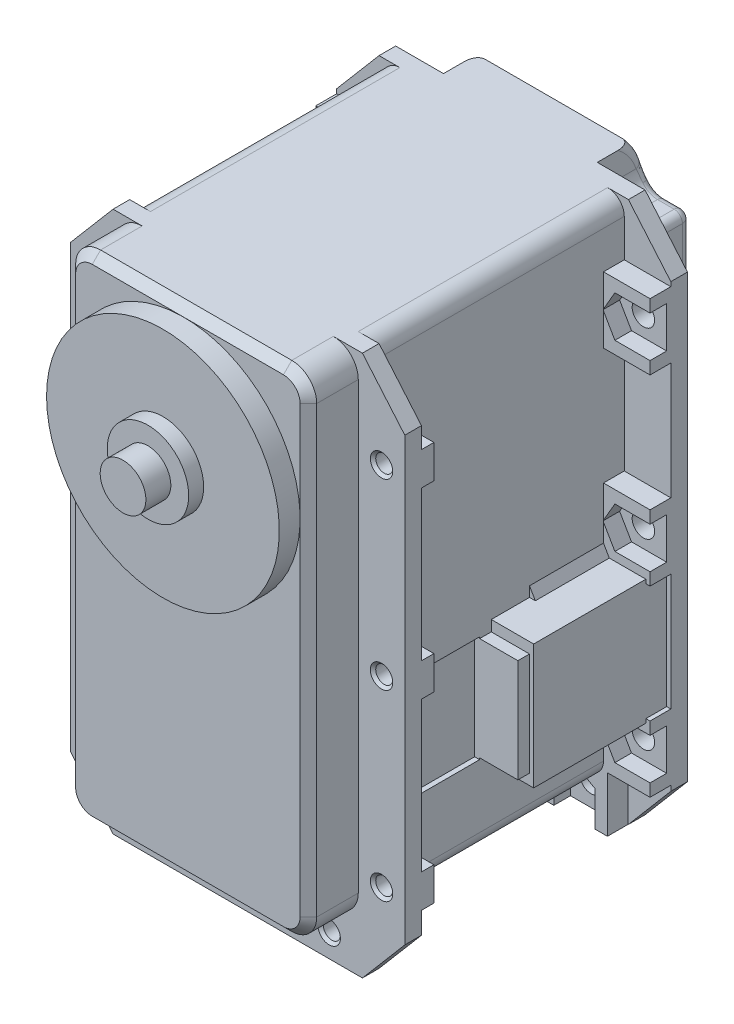
SolidWorks part; units mm, degrees
note: '?' marks a value the reader was unsure of.
material "Custom Plastic"
ref_plane "Front Plane" through (0, 0, 0) normal (0, 0, 1) x (1, 0, 0)
ref_plane "Top Plane" through (0, 0, 0) normal (0, 1, 0) x (1, 0, 0)
ref_plane "Right Plane" through (0, 0, 0) normal (1, 0, 0) x (0, 0, -1)
ref_plane "Plane1" through (9.25, 0, 0) normal (1, 0, 0) x (0, 0, -1)
sketch "Sketch1" plane through (9.25, 0, 0) normal (1, 0, 0) x (0, 0, -1)
  line L0 (21, 14.5) -> (21, 9.5)
  line L1 (21, 9.5) -> (23, 9.5)
  arc A0 (23, 9.5) -> (21, 14.5) centre (15.75, 9.5) ccw
extrude "Boss-Extrude1" add sketch "Sketch1" against normal blind 18.5
ref_plane "Plane2" through (0, 9.5, 0) normal (0, -1, 0) x (1, 0, 0)
sketch "Sketch2" plane through (0, 9.5, 0) normal (0, -1, 0) x (1, 0, 0)
  line L0 (-15.8711, -21) -> (-15.8711, -23)
  line L1 (-15.8711, -23) -> (-9.25, -23)
  line L2 (-9.25, -23) -> (-9.25, -21)
  line L3 (-9.25, -21) -> (-15.8711, -21)
extrude "Boss-Extrude2" add sketch "Sketch2" against normal blind 5
sketch "Sketch3" plane through (0, 9.5, 0) normal (0, -1, 0) x (1, 0, 0)
  line L0 (9.25, -21) -> (9.25, -23)
  line L1 (9.25, -23) -> (20.1, -23)
  line L2 (20.1, -23) -> (20.1, -21)
  line L3 (20.1, -21) -> (9.25, -21)
extrude "Boss-Extrude3" add sketch "Sketch3" against normal blind 5
sketch "Sketch4" plane through (0, 9.5, 0) normal (0, -1, 0) x (1, 0, 0)
  line L0 (20.1, -21) -> (20.1, -23)
  line L1 (20.1, -23) -> (-15.8711, -23)
  line L2 (-15.8711, -23) -> (-15.8711, -21)
  line L3 (-15.8711, -21) -> (20.1, -21)
extrude "Boss-Extrude4" add sketch "Sketch4" along normal blind 60.1
sketch "Sketch5" plane through (0, 0, -21) normal (0, 0, 1) x (1, 0, 0)
  line L0 (-15.8711, -50.6) -> (-15.8711, 14.5)
  line L1 (-15.8711, 14.5) -> (20.1, 14.5)
  line L2 (20.1, 14.5) -> (20.1, -50.6)
  line L3 (20.1, -50.6) -> (-15.8711, -50.6)
extrude "Boss-Extrude5" add sketch "Sketch5" along normal blind 6.5
sketch "Sketch6" plane through (0, 0, -23) normal (0, 0, -1) x (-1, 0, 0)
  line L0 (15.8711, -50.6) -> (15.8711, 14.5)
  line L1 (15.8711, 14.5) -> (9.25, 14.5)
  line L2 (9.25, 14.5) -> (9.25, -45)
  line L3 (9.25, -45) -> (-9.25, -45)
  line L4 (-9.25, -45) -> (-9.25, 14.5)
  line L5 (-9.25, 14.5) -> (-20.1, 14.5)
  line L6 (-20.1, 14.5) -> (-20.1, -50.6)
  line L7 (-20.1, -50.6) -> (15.8711, -50.6)
extrude "Cut-Extrude1" cut sketch "Sketch6" against normal blind 2
sketch "Sketch7" plane through (0, 0, -14.5) normal (0, 0, 1) x (1, 0, 0)
  line L0 (-15.8711, -20.475) -> (-14.5, -18.1003)
  line L1 (-14.5, -18.1003) -> (-14.5, -17.8997)
  line L2 (-14.5, -17.8997) -> (-15.8711, -15.525)
  line L3 (-15.8711, -15.525) -> (-15.8711, 1.525)
  line L4 (-15.8711, 1.525) -> (-14.5, 3.8997)
  line L5 (-14.5, 3.8997) -> (-14.5, 4.1003)
  line L6 (-14.5, 4.1003) -> (-15.8711, 6.475)
  line L7 (-15.8711, 6.475) -> (-15.8711, 14.5)
  line L8 (-15.8711, 14.5) -> (20.1, 14.5)
  line L9 (20.1, 14.5) -> (20.1, -50.6)
  line L10 (20.1, -50.6) -> (-15.8711, -50.6)
  line L11 (-15.8711, -50.6) -> (-15.8711, -42.475)
  line L12 (-15.8711, -42.475) -> (-14.5, -40.1003)
  line L13 (-14.5, -40.1003) -> (-14.5, -39.8997)
  line L14 (-14.5, -39.8997) -> (-15.8711, -37.525)
  line L15 (-15.8711, -37.525) -> (-15.8711, -20.475)
extrude "Boss-Extrude6" add sketch "Sketch7" along normal blind 2
sketch "Sketch8" plane through (0, 0, -21) normal (0, 0, -1) x (-1, 0, 0)
  line L0 (15.8711, -50.6) -> (15.8711, 14.5)
  line L1 (15.8711, 14.5) -> (9.25, 14.5)
  line L2 (9.25, 14.5) -> (9.25, -45)
  line L3 (9.25, -45) -> (-9.25, -45)
  line L4 (-9.25, -45) -> (-9.25, 14.5)
  line L5 (-9.25, 14.5) -> (-20.1, 14.5)
  line L6 (-20.1, 14.5) -> (-20.1, -50.6)
  line L7 (-20.1, -50.6) -> (15.8711, -50.6)
extrude "Cut-Extrude2" cut sketch "Sketch8" against normal blind 4
sketch "Sketch9" plane through (0, 0, -12.5) normal (0, 0, 1) x (1, 0, 0)
  line L0 (20.1, 14.5) -> (20.1, -50.6)
  line L1 (20.1, -50.6) -> (-15.8711, -50.6)
  line L2 (-15.8711, -50.6) -> (-15.8711, -42.475)
  line L3 (-15.8711, -42.475) -> (-14.5, -40.1003)
  line L4 (-14.5, -40.1003) -> (-14.5, 14.5)
  line L5 (-14.5, 14.5) -> (20.1, 14.5)
extrude "Boss-Extrude7" add sketch "Sketch9" along normal blind 29.5
sketch "Sketch10" plane through (0, 0, 17) normal (0, 0, 1) x (1, 0, 0)
  line L0 (14.5, 14.5) -> (14.5, -45)
  line L1 (14.5, -45) -> (-14.5, -45)
  line L2 (-14.5, -45) -> (-14.5, -40.1003)
  line L3 (-14.5, -40.1003) -> (-15.8711, -42.475)
  line L4 (-15.8711, -42.475) -> (-15.8711, -50.6)
  line L5 (-15.8711, -50.6) -> (20.1, -50.6)
  line L6 (20.1, -50.6) -> (20.1, 14.5)
  line L7 (20.1, 14.5) -> (14.5, 14.5)
extrude "Cut-Extrude3" cut sketch "Sketch10" against normal blind 29.5
sketch "Sketch11" plane through (0, 0, -12.5) normal (0, 0, 1) x (1, 0, 0)
  line L0 (-13.475, -46.3711) -> (-13.475, -50.6)
  line L1 (-13.475, -50.6) -> (-8.525, -50.6)
  line L2 (-8.525, -50.6) -> (-8.525, -46.3711)
  line L3 (-8.525, -46.3711) -> (-11, -44.9421)
  line L4 (-11, -44.9421) -> (-13.475, -46.3711)
extrude "Cut-Extrude4" cut sketch "Sketch11" against normal blind 2
sketch "Sketch12" plane through (0, 0, -12.5) normal (0, 0, 1) x (1, 0, 0)
  line L0 (8.525, -46.3711) -> (8.525, -50.6)
  line L1 (8.525, -50.6) -> (13.475, -50.6)
  line L2 (13.475, -50.6) -> (13.475, -46.3711)
  line L3 (13.475, -46.3711) -> (11, -44.9421)
  line L4 (11, -44.9421) -> (8.525, -46.3711)
extrude "Cut-Extrude5" cut sketch "Sketch12" against normal blind 2
sketch "Sketch13" plane through (0, 0, -12.5) normal (0, 0, 1) x (1, 0, 0)
  line L0 (15.8711, -42.475) -> (20.1, -42.475)
  line L1 (20.1, -42.475) -> (20.1, -37.525)
  line L2 (20.1, -37.525) -> (15.8711, -37.525)
  line L3 (15.8711, -37.525) -> (14.4421, -40)
  line L4 (14.4421, -40) -> (15.8711, -42.475)
extrude "Cut-Extrude6" cut sketch "Sketch13" against normal blind 2
sketch3d "3DSketch1"
  point P0 (0.3206, -15.6432, -2.4982)
  point P1 (0.3206, 84.3568, -2.4982)
ref_axis "Axis1" through (0.3206, -15.6432, -2.4982) along (0, 1, 0)?
pattern_linear "LPattern1" count 3 spacing 22 along (0, 1, 0) of "Cut-Extrude6"
ref_plane "Plane3" through (0, 0, -14.5) normal (0, 0, -1) x (-1, 0, 0)
sketch "Sketch14" plane through (0, 0, -14.5) normal (0, 0, -1) x (-1, 0, 0)
  line L0 (14.4421, -40) -> (14.5, -40.1003)
  line L1 (14.5, -40.1003) -> (14.5, -39.8997)
  line L2 (14.5, -39.8997) -> (14.4421, -40)
extrude "Cut-Extrude7" cut sketch "Sketch14" against normal blind 2
sketch3d "3DSketch2"
  point P0 (0.2957, -15.6557, -2.4823)
  point P1 (0.2957, 84.3443, -2.4823)
ref_axis "Axis2" through (0.2957, -15.6557, -2.4823) along (0, 1, 0)?
pattern_linear "LPattern2" count 3 spacing 22 along (0, 1, 0) of "Cut-Extrude7"
sketch "Sketch15" plane through (-15.8711, 0, 0) normal (-1, 0, 0) x (0, 0, 1)
  line L0 (-12.5, 14.5) -> (-12.5, 6.475)
  line L1 (-12.5, 6.475) -> (-14.5, 6.475)
  line L2 (-14.5, 6.475) -> (-14.5, 1.525)
  line L3 (-14.5, 1.525) -> (-12.5, 1.525)
  line L4 (-12.5, 1.525) -> (-12.5, -15.525)
  line L5 (-12.5, -15.525) -> (-14.5, -15.525)
  line L6 (-14.5, -15.525) -> (-14.5, -20.475)
  line L7 (-14.5, -20.475) -> (-12.5, -20.475)
  line L8 (-12.5, -20.475) -> (-12.5, -37.525)
  line L9 (-12.5, -37.525) -> (-14.5, -37.525)
  line L10 (-14.5, -37.525) -> (-14.5, -42.475)
  line L11 (-14.5, -42.475) -> (-12.5, -42.475)
  line L12 (-12.5, -42.475) -> (-12.5, -50.6)
  line L13 (-12.5, -50.6) -> (-17, -50.6)
  line L14 (-17, -50.6) -> (-17, 14.5)
  line L15 (-17, 14.5) -> (-12.5, 14.5)
extrude "Boss-Extrude8" add sketch "Sketch15" along normal blind 4.2289
sketch "Sketch16" plane through (-14.5, 0, 0) normal (-1, 0, 0) x (0, 0, 1)
  line L0 (15, -45) -> (15, 14.5)
  line L1 (15, 14.5) -> (17, 14.5)
  line L2 (17, 14.5) -> (17, -45)
  line L3 (17, -45) -> (15, -45)
extrude "Boss-Extrude9" add sketch "Sketch16" along normal blind 5.6
sketch "Sketch17" plane through (0, -45, 0) normal (0, -1, 0) x (1, 0, 0)
  line L0 (14.5, 15) -> (-20.1, 15)
  line L1 (-20.1, 15) -> (-20.1, 17)
  line L2 (-20.1, 17) -> (14.5, 17)
  line L3 (14.5, 17) -> (14.5, 15)
extrude "Boss-Extrude10" add sketch "Sketch17" along normal blind 5.6
sketch "Sketch18" plane through (14.5, 0, 0) normal (1, 0, 0) x (0, 0, -1)
  line L0 (-15, -50.6) -> (-17, -50.6)
  line L1 (-17, -50.6) -> (-17, 14.5)
  line L2 (-17, 14.5) -> (-15, 14.5)
  line L3 (-15, 14.5) -> (-15, -50.6)
extrude "Boss-Extrude11" add sketch "Sketch18" along normal blind 5.6
sketch "Sketch19" plane through (14.5, 0, 0) normal (1, 0, 0) x (0, 0, -1)
  line L0 (-1, -21.5) -> (12.5, -21.5)
  line L1 (12.5, -21.5) -> (12.5, -36.5)
  line L2 (12.5, -36.5) -> (-1, -36.5)
  line L3 (-1, -36.5) -> (-1, -21.5)
extrude "Boss-Extrude12" add sketch "Sketch19" along normal blind 5.1
sketch "Sketch20" plane through (0, 0, 1) normal (0, 0, 1) x (1, 0, 0)
  line L0 (19.1, -35.21) -> (14.5, -35.21)
  line L1 (14.5, -35.21) -> (14.5, -22.79)
  line L2 (14.5, -22.79) -> (19.1, -22.79)
  line L3 (19.1, -22.79) -> (19.1, -35.21)
extrude "Boss-Extrude13" add sketch "Sketch20" along normal blind 1.4
sketch "Sketch21" plane through (14.5, 0, 0) normal (1, 0, 0) x (0, 0, -1)
  line L0 (-2.4, -35.4) -> (-2.4, -22.6)
  line L1 (-2.4, -22.6) -> (-12.5, -22.6)
  line L2 (-12.5, -22.6) -> (-12.5, -35.4)
  line L3 (-12.5, -35.4) -> (-2.4, -35.4)
extrude "Cut-Extrude8" cut sketch "Sketch21" against normal blind 0.6
sketch "Sketch22" plane through (-14.5, 0, 0) normal (-1, 0, 0) x (0, 0, 1)
  line L0 (1, -36.5) -> (-12.5, -36.5)
  line L1 (-12.5, -36.5) -> (-12.5, -21.5)
  line L2 (-12.5, -21.5) -> (1, -21.5)
  line L3 (1, -21.5) -> (1, -36.5)
extrude "Boss-Extrude14" add sketch "Sketch22" along normal blind 5.1
sketch "Sketch23" plane through (0, 0, 1) normal (0, 0, 1) x (1, 0, 0)
  line L0 (-19.1, -22.79) -> (-14.5, -22.79)
  line L1 (-14.5, -22.79) -> (-14.5, -35.21)
  line L2 (-14.5, -35.21) -> (-19.1, -35.21)
  line L3 (-19.1, -35.21) -> (-19.1, -22.79)
extrude "Boss-Extrude15" add sketch "Sketch23" along normal blind 1.4
sketch "Sketch24" plane through (-14.5, 0, 0) normal (-1, 0, 0) x (0, 0, 1)
  line L0 (2.4, -22.6) -> (2.4, -35.4)
  line L1 (2.4, -35.4) -> (12.5, -35.4)
  line L2 (12.5, -35.4) -> (12.5, -22.6)
  line L3 (12.5, -22.6) -> (2.4, -22.6)
extrude "Cut-Extrude9" cut sketch "Sketch24" against normal blind 0.6
sketch "Sketch25" plane through (0, -50.6, 0) normal (0, -1, 0) x (1, 0, 0)
  line L0 (7.025, -15) -> (7.025, -12.5)
  line L1 (7.025, -12.5) -> (-7.025, -12.5)
  line L2 (-7.025, -12.5) -> (-7.025, -15)
  line L3 (-7.025, -15) -> (7.025, -15)
extrude "Cut-Extrude10" cut sketch "Sketch25" against normal blind 5.6
sketch "Sketch26" plane through (20.1, 0, 0) normal (1, 0, 0) x (0, 0, -1)
  line L0 (15, -21.975) -> (12.5, -21.975)
  line L1 (12.5, -21.975) -> (12.5, -36.025)
  line L2 (12.5, -36.025) -> (15, -36.025)
  line L3 (15, -36.025) -> (15, -21.975)
extrude "Cut-Extrude11" cut sketch "Sketch26" against normal blind 0.5
sketch "Sketch27" plane through (20.1, 0, 0) normal (1, 0, 0) x (0, 0, -1)
  line L0 (15, 0.025) -> (12.5, 0.025)
  line L1 (12.5, 0.025) -> (12.5, -14.025)
  line L2 (12.5, -14.025) -> (15, -14.025)
  line L3 (15, -14.025) -> (15, 0.025)
extrude "Cut-Extrude12" cut sketch "Sketch27" against normal blind 5.6
sketch "Sketch28" plane through (20.1, 0, 0) normal (1, 0, 0) x (0, 0, -1)
  line L0 (12.5, 7.975) -> (15, 7.975)
  line L1 (15, 7.975) -> (15, 14.5)
  line L2 (15, 14.5) -> (12.5, 14.5)
  line L3 (12.5, 14.5) -> (12.5, 7.975)
extrude "Cut-Extrude13" cut sketch "Sketch28" against normal blind 5.6
sketch "Sketch29" plane through (-20.1, 0, 0) normal (-1, 0, 0) x (0, 0, 1)
  line L0 (-15, 7.975) -> (-12.5, 7.975)
  line L1 (-12.5, 7.975) -> (-12.5, 14.5)
  line L2 (-12.5, 14.5) -> (-15, 14.5)
  line L3 (-15, 14.5) -> (-15, 7.975)
extrude "Cut-Extrude14" cut sketch "Sketch29" against normal blind 5.6
sketch "Sketch30" plane through (-20.1, 0, 0) normal (-1, 0, 0) x (0, 0, 1)
  line L0 (-12.5, 0.025) -> (-15, 0.025)
  line L1 (-15, 0.025) -> (-15, -14.025)
  line L2 (-15, -14.025) -> (-12.5, -14.025)
  line L3 (-12.5, -14.025) -> (-12.5, 0.025)
extrude "Cut-Extrude15" cut sketch "Sketch30" against normal blind 5.6
sketch "Sketch31" plane through (-20.1, 0, 0) normal (-1, 0, 0) x (0, 0, 1)
  line L0 (-15, -36.025) -> (-12.5, -36.025)
  line L1 (-12.5, -36.025) -> (-12.5, -21.975)
  line L2 (-12.5, -21.975) -> (-15, -21.975)
  line L3 (-15, -21.975) -> (-15, -36.025)
extrude "Cut-Extrude16" cut sketch "Sketch31" against normal blind 0.5
sketch "Sketch32" plane through (0, -45, 0) normal (0, -1, 0) x (1, 0, 0)
  line L0 (-13, 13.5) -> (-13, 15)
  line L1 (-13, 15) -> (-9, 15)
  line L2 (-9, 15) -> (-9, 13.5)
  line L3 (-9, 13.5) -> (-13, 13.5)
extrude "Boss-Extrude16" add sketch "Sketch32" along normal blind 5.6
sketch "Sketch33" plane through (0, -45, 0) normal (0, -1, 0) x (1, 0, 0)
  line L0 (9, 13.5) -> (9, 15)
  line L1 (9, 15) -> (13, 15)
  line L2 (13, 15) -> (13, 13.5)
  line L3 (13, 13.5) -> (9, 13.5)
extrude "Boss-Extrude17" add sketch "Sketch33" along normal blind 5.6
sketch "Sketch34" plane through (14.5, 0, 0) normal (1, 0, 0) x (0, 0, -1)
  line L0 (-13.5, 2) -> (-15, 2)
  line L1 (-15, 2) -> (-15, 6)
  line L2 (-15, 6) -> (-13.5, 6)
  line L3 (-13.5, 6) -> (-13.5, 2)
extrude "Boss-Extrude18" add sketch "Sketch34" along normal blind 5.6
sketch3d "3DSketch3"
  point P0 (0.0081, -16.3123, -2.1724)
  point P1 (0.0081, -116.3123, -2.1724)
ref_axis "Axis3" through (0.0081, -16.3123, -2.1724) along (0, -1, 0)?
pattern_linear "LPattern3" count 3 spacing 22 along (0, -1, 0) of "Boss-Extrude18"
sketch "Sketch35" plane through (-14.5, 0, 0) normal (-1, 0, 0) x (0, 0, 1)
  line L0 (15, 2) -> (13.5, 2)
  line L1 (13.5, 2) -> (13.5, 6)
  line L2 (13.5, 6) -> (15, 6)
  line L3 (15, 6) -> (15, 2)
extrude "Boss-Extrude19" add sketch "Sketch35" along normal blind 5.6
pattern_linear "LPattern4" count 3 spacing 22 along (0, -1, 0) of "Boss-Extrude19"
sketch "Sketch36" plane through (0, 0, -17) normal (0, 0, -1) x (-1, 0, 0)
  line L0 (-14.5, 9.25) -> (-9.25, 9.25)
  line L1 (-9.25, 9.25) -> (-9.25, -39.75)
  line L2 (-9.25, -39.75) -> (-14.5, -39.75)
  line L3 (-14.5, -39.75) -> (-14.5, 9.25)
extrude "Boss-Extrude20" add sketch "Sketch36" along normal blind 6
sketch "Sketch37" plane through (0, 0, -17) normal (0, 0, -1) x (-1, 0, 0)
  line L0 (14.5, -39.75) -> (9.25, -39.75)
  line L1 (9.25, -39.75) -> (9.25, 9.25)
  line L2 (9.25, 9.25) -> (14.5, 9.25)
  line L3 (14.5, 9.25) -> (14.5, -39.75)
extrude "Boss-Extrude21" add sketch "Sketch37" along normal blind 6
sketch "Sketch38" plane through (0, 0, -12.5) normal (0, 0, 1) x (1, 0, 0)
  line L0 (15.2, -21.5) -> (14.5, -21.5)
  line L1 (14.5, -21.5) -> (14.5, -20.2876)
  line L2 (14.5, -20.2876) -> (15.2, -21.5)
extrude "Boss-Extrude22" add sketch "Sketch38" along normal blind 8.9
sketch "Sketch39" plane through (0, 0, -12.5) normal (0, 0, 1) x (1, 0, 0)
  line L0 (14.975, -43.975) -> (14.975, -50.6)
  line L1 (14.975, -50.6) -> (20.1, -50.6)
  line L2 (20.1, -50.6) -> (20.1, -43.975)
  line L3 (20.1, -43.975) -> (14.975, -43.975)
extrude "Cut-Extrude17" cut sketch "Sketch39" against normal blind 2.5
sketch "Sketch40" plane through (0, -50.6, 0) normal (0, -1, 0) x (1, 0, 0)
  line L0 (-20.1, -15) -> (-14.975, -15)
  line L1 (-14.975, -15) -> (-14.975, -12.5)
  line L2 (-14.975, -12.5) -> (-20.1, -12.5)
  line L3 (-20.1, -12.5) -> (-20.1, -15)
extrude "Cut-Extrude18" cut sketch "Sketch40" against normal blind 6.625
sketch "Sketch41" plane through (0, 0, 17) normal (0, 0, 1) x (1, 0, 0)
  line L0 (-14.5, -45) -> (-14.5, 14.5)
  line L1 (-14.5, 14.5) -> (14.5, 14.5)
  line L2 (14.5, 14.5) -> (14.5, -45)
  line L3 (14.5, -45) -> (-14.5, -45)
extrude "Boss-Extrude23" add sketch "Sketch41" along normal blind 6
sketch "Sketch42" plane through (0, 0, -12.5) normal (0, 0, 1) x (1, 0, 0)
  line L0 (-15.2, -21.5) -> (-14.5, -20.2876)
  line L1 (-14.5, -20.2876) -> (-14.5, -21.5)
  line L2 (-14.5, -21.5) -> (-15.2, -21.5)
extrude "Boss-Extrude24" add sketch "Sketch42" along normal blind 8.9
sketch "Sketch43" plane through (-14.5, 0, 0) normal (-1, 0, 0) x (0, 0, 1)
  line L0 (-8.8, -13.45) -> (-5, -13.45)
  line L1 (-5, -13.45) -> (-5, -7.55)
  line L2 (-5, -7.55) -> (-8.8, -7.55)
  line L3 (-8.8, -7.55) -> (-8.8, -13.45)
extrude "Cut-Extrude19" cut sketch "Sketch43" against normal blind 1
hole_wizard "Hole1" positions "Sketch45" profile "Sketch44" legacy
sketch "Sketch45" plane through (0, 0, -23) normal (0, 0, -1) x (-1, 0, 0)
  point P0 (0, 0)
sketch "Sketch44" plane through (0, 0, -23) normal (1, 0, 0) x (0, 1, 0)
  line L0 (0, 0) -> (0, 1)
  line L1 (0, 1) -> (7.5, 1)
  line L2 (7.5, 1) -> (7.5, 0)
  line L3 (7.5, 0) -> (0, 0)
  line L4 (0, 110) -> (0, -10) construction
  dimension "Diameter" = 15
  dimension "Depth" = 1
ref_plane "Plane4" through (0, 0, 0) normal (0, -1, 0) x (1, 0, 0)
sketch "Sketch46" plane through (0, 0, 0) normal (0, -1, 0) x (1, 0, 0)
  line L0 (2.75, 30.8) -> (0, 30.8)
  line L1 (0, 30.8) -> (0, 23)
  line L2 (0, 23) -> (5, 23)
  line L3 (5, 23) -> (5, 23.5)
  line L4 (5, 23.5) -> (14, 23.5)
  line L5 (14, 23.5) -> (14, 26)
  line L6 (14, 26) -> (5, 26)
  line L7 (5, 26) -> (5, 27.8)
  line L8 (5, 27.8) -> (2.75, 27.8)
  line L9 (2.75, 27.8) -> (2.75, 30.8)
  line L10 (0, 30.8) -> (0, 23) construction
revolve "Revolve1" add sketch "Sketch46" angle 360 about L10 reverse direction yes
sketch "Sketch47" plane through (0, 0, 0) normal (0, -1, 0) x (1, 0, 0)
  line L0 (5, -22) -> (0, -22)
  line L1 (0, -22) -> (0, -24.5)
  line L2 (0, -24.5) -> (4, -24.5)
  line L3 (4, -24.5) -> (4, -22.3)
  line L4 (4, -22.3) -> (5, -22.3)
  line L5 (5, -22.3) -> (5, -22)
  line L6 (0, -22) -> (0, -24.5) construction
revolve "Revolve2" add sketch "Sketch47" angle 360 about L6 reverse direction yes
hole_wizard "Hole2" positions "Sketch49" profile "Sketch48" legacy
sketch "Sketch49" plane through (0, 0, -14.5) normal (0, 0, 1) x (1, 0, 0)
  point P0 (17.3, -40)
sketch "Sketch48" plane through (17.3, -40, -14.5) normal (1, 0, 0) x (0, -1, 0)
  line L0 (0, 0) -> (0, 10)
  line L1 (0, 10) -> (1.35, 10)
  line L2 (1.35, 10) -> (1.35, 0)
  line L3 (1.35, 0) -> (0, 0)
  line L4 (0, 110) -> (0, -10) construction
  dimension "Diameter" = 2.7
  dimension "Depth" = 10
sketch3d "3DSketch4"
  point P0 (0.0008, -15.7705, 0.4564)
  point P1 (0.0008, 84.2295, 0.4564)
ref_axis "Axis4" through (0.0008, -15.7705, 0.4564) along (0, 1, 0)?
pattern_linear "LPattern5" count 3 spacing 22 along (0, 1, 0) of "Hole2"
hole_wizard "Hole3" positions "Sketch51" profile "Sketch50" legacy
sketch "Sketch51" plane through (0, 0, -14.5) normal (0, 0, 1) x (1, 0, 0)
  point P0 (-17.3, -40)
sketch "Sketch50" plane through (-17.3, -40, -14.5) normal (1, 0, 0) x (0, -1, 0)
  line L0 (0, 0) -> (0, 10)
  line L1 (0, 10) -> (1.35, 10)
  line L2 (1.35, 10) -> (1.35, 0)
  line L3 (1.35, 0) -> (0, 0)
  line L4 (0, 110) -> (0, -10) construction
  dimension "Diameter" = 2.7
  dimension "Depth" = 10
sketch3d "3DSketch5"
  point P0 (-0.0021, -15.7694, 0.4644)
  point P1 (-0.0021, 84.2306, 0.4644)
ref_axis "Axis5" through (-0.0021, -15.7694, 0.4644) along (0, 1, 0)?
pattern_linear "LPattern6" count 3 spacing 22 along (0, 1, 0) of "Hole3"
hole_wizard "Hole4" positions "Sketch53" profile "Sketch52" legacy
sketch "Sketch53" plane through (0, 0, -14.5) normal (0, 0, 1) x (1, 0, 0)
  point P0 (11, -47.8)
sketch "Sketch52" plane through (11, -47.8, -14.5) normal (1, 0, 0) x (0, -1, 0)
  line L0 (0, 0) -> (0, 10)
  line L1 (0, 10) -> (1.35, 10)
  line L2 (1.35, 10) -> (1.35, 0)
  line L3 (1.35, 0) -> (0, 0)
  line L4 (0, 110) -> (0, -10) construction
  dimension "Diameter" = 2.7
  dimension "Depth" = 10
hole_wizard "Hole5" positions "Sketch55" profile "Sketch54" legacy
sketch "Sketch55" plane through (0, 0, -14.5) normal (0, 0, 1) x (1, 0, 0)
  point P0 (-11, -47.8)
sketch "Sketch54" plane through (-11, -47.8, -14.5) normal (1, 0, 0) x (0, -1, 0)
  line L0 (0, 0) -> (0, 10)
  line L1 (0, 10) -> (1.35, 10)
  line L2 (1.35, 10) -> (1.35, 0)
  line L3 (1.35, 0) -> (0, 0)
  line L4 (0, 110) -> (0, -10) construction
  dimension "Diameter" = 2.7
  dimension "Depth" = 10
hole_wizard "Hole6" positions "Sketch57" profile "Sketch56" legacy
sketch "Sketch57" plane through (0, 0, 17) normal (0, 0, 1) x (1, 0, 0)
  point P0 (-11, -47.8)
sketch "Sketch56" plane through (-11, -47.8, 17) normal (1, 0, 0) x (0, -1, 0)
  line L0 (0, 0) -> (0, 41.5)
  line L1 (0, 41.5) -> (1.025, 41.5)
  line L2 (1.025, 41.5) -> (1.025, 0)
  line L3 (1.025, 0) -> (0, 0)
  line L4 (0, 110) -> (0, -10) construction
  dimension "Diameter" = 2.05
  dimension "Depth" = 41.5
hole_wizard "Hole7" positions "Sketch59" profile "Sketch58" legacy
sketch "Sketch59" plane through (0, 0, 17) normal (0, 0, 1) x (1, 0, 0)
  point P0 (-17.3, 4)
sketch "Sketch58" plane through (-17.3, 4, 17) normal (1, 0, 0) x (0, -1, 0)
  line L0 (0, 0) -> (0, 41.5)
  line L1 (0, 41.5) -> (1.025, 41.5)
  line L2 (1.025, 41.5) -> (1.025, 0)
  line L3 (1.025, 0) -> (0, 0)
  line L4 (0, 110) -> (0, -10) construction
  dimension "Diameter" = 2.05
  dimension "Depth" = 41.5
sketch3d "3DSketch6"
  point P0 (0.0074, -15.7601, 0.4711)
  point P1 (0.0074, -115.7601, 0.4711)
ref_axis "Axis6" through (0.0074, -15.7601, 0.4711) along (0, -1, 0)?
pattern_linear "LPattern7" count 3 spacing 22 along (0, -1, 0) of "Hole7"
hole_wizard "Hole8" positions "Sketch61" profile "Sketch60" legacy
sketch "Sketch61" plane through (0, 0, 17) normal (0, 0, 1) x (1, 0, 0)
  point P0 (11, -47.8)
sketch "Sketch60" plane through (11, -47.8, 17) normal (1, 0, 0) x (0, -1, 0)
  line L0 (0, 0) -> (0, 41.5)
  line L1 (0, 41.5) -> (1.025, 41.5)
  line L2 (1.025, 41.5) -> (1.025, 0)
  line L3 (1.025, 0) -> (0, 0)
  line L4 (0, 110) -> (0, -10) construction
  dimension "Diameter" = 2.05
  dimension "Depth" = 41.5
hole_wizard "Hole9" positions "Sketch63" profile "Sketch62" legacy
sketch "Sketch63" plane through (0, 0, 17) normal (0, 0, 1) x (1, 0, 0)
  point P0 (17.3, -40)
sketch "Sketch62" plane through (17.3, -40, 17) normal (1, 0, 0) x (0, -1, 0)
  line L0 (0, 0) -> (0, 41.5)
  line L1 (0, 41.5) -> (1.025, 41.5)
  line L2 (1.025, 41.5) -> (1.025, 0)
  line L3 (1.025, 0) -> (0, 0)
  line L4 (0, 110) -> (0, -10) construction
  dimension "Diameter" = 2.05
  dimension "Depth" = 41.5
sketch3d "3DSketch7"
  point P0 (0.0082, -15.7491, 0.4633)
  point P1 (0.0082, 84.2509, 0.4633)
ref_axis "Axis7" through (0.0082, -15.7491, 0.4633) along (0, 1, 0)?
pattern_linear "LPattern8" count 3 spacing 22 along (0, 1, 0) of "Hole9"
hole_wizard "Hole10" positions "Sketch65" profile "Sketch64" legacy
sketch "Sketch65" plane through (0, 0, -24.5) normal (0, 0, -1) x (-1, 0, 0)
  point P0 (0, 0)
sketch "Sketch64" plane through (0, 0, -24.5) normal (1, 0, 0) x (0, 1, 0)
  line L0 (0, 0) -> (0, 2.2)
  line L1 (0, 2.2) -> (1.6, 2.2)
  line L2 (1.6, 2.2) -> (1.6, 0)
  line L3 (1.6, 0) -> (0, 0)
  line L4 (0, 110) -> (0, -10) construction
  dimension "Diameter" = 3.2
  dimension "Depth" = 2.2
fillet "Fillet1" radius 2 1 edges at (-14.5, -45, 1.25) tangent propagation no
fillet "Fillet2" radius 2 1 edges at (14.5, -45, 1.25) tangent propagation no
fillet "Fillet3" radius 2.25 1 edges at (-9.25, 9.25, -20) tangent propagation no
fillet "Fillet4" radius 2.25 1 edges at (9.25, 9.25, -20) tangent propagation no
fillet "Fillet5" radius 2.25 1 edges at (9.25, -39.75, -20) tangent propagation no
fillet "Fillet6" radius 2.25 1 edges at (-9.25, -39.75, -20) tangent propagation no
fillet "Fillet7" radius 3 1 edges at (-14.5, -45, 20) tangent propagation no
fillet "Fillet8" radius 3 1 edges tangent propagation no
fillet "Fillet9" radius 3 1 edges tangent propagation no
fillet "Fillet10" radius 3 1 edges at (14.5, -45, 20) tangent propagation no
chamfer "Chamfer1" distance 0.325 angle 45 1 edges at (18.325, -18, 17)
chamfer "Chamfer2" distance 5.1 angle 49.635 1 edges at (-20.1, -50.6, -16) first distance on face at (0, -50.6, -14.1)
chamfer "Chamfer3" distance 5.1 angle 49.635 1 edges at (-20.1, 14.5, 16) first distance on face at (-0.0325, 14.5, 1.15)
chamfer "Chamfer4" distance 5.1 angle 49.635 1 edges at (20.1, -50.6, 16) first distance on face at (0, -50.6, 14.8333)
chamfer "Chamfer5" distance 6 angle 40.365 1 edges at (-20.1, 14.5, -16) first distance on face at (-20.1, -17.5786, -13.9643)
chamfer "Chamfer6" distance 6 angle 40.365 1 edges at (20.1, -50.6, -16) first distance on face at (20.1, -18.0071, -13.9643)
chamfer "Chamfer7" distance 5.1 angle 49.635 1 edges at (20.1, 14.5, -16) first distance on face at (0.86, 14.5, 1.15)
chamfer "Chamfer8" distance 6 angle 40.365 1 edges at (20.1, 14.5, 16) first distance on face at (20.1, -17.2625, 14.6875)
chamfer "Chamfer9" distance 0.325 angle 45 1 edges at (-9.975, -47.8, 17)
chamfer "Chamfer10" distance 0.325 angle 45 1 edges at (-16.275, -40, 17)
chamfer "Chamfer11" distance 0.325 angle 45 1 edges at (-16.275, -18, 17)
chamfer "Chamfer12" distance 6 angle 40.365 1 edges at (-20.1, -50.6, 16) first distance on face at (-20.1, -18.7625, 14.6875)
chamfer "Chamfer13" distance 0.325 angle 45 1 edges at (-16.275, 4, 17)
chamfer "Chamfer14" distance 0.325 angle 45 1 edges at (12.025, -47.8, 17)
chamfer "Chamfer15" distance 0.325 angle 45 1 edges at (18.325, -40, 17)
chamfer "Chamfer16" distance 0.325 angle 45 1 edges at (18.325, 4, 17)
chamfer "Chamfer17" distance 1 angle 45 8 edges at (14.5, -15.25, 23) (13.6213, 13.6213, 23) (13.6213, -44.1213, 23) (0, 14.5, 23) (0, -45, 23) (-13.6213, 13.6213, 23) (-13.6213, -44.1213, 23) (-14.5, -15.25, 23)
fillet "Fillet11" radius 1 1 edges at (13, -44.9365, 14.25) tangent propagation no
fillet "Fillet12" radius 1 1 edges at (-13, -44.9365, 14.25) tangent propagation no
fillet "Fillet13" radius 1 1 edges at (-9, -45, 14.25) tangent propagation no
fillet "Fillet14" radius 1 1 edges at (9, -45, 14.25) tangent propagation no
fillet "Fillet15" radius 1 1 edges at (14.5, -38, 14.25) tangent propagation no
fillet "Fillet16" radius 1 1 edges at (14.5, -16, 14.25) tangent propagation no
fillet "Fillet17" radius 1 1 edges at (14.5, 6, 14.25) tangent propagation no
fillet "Fillet18" radius 1 1 edges at (-14.5, -16, 14.25) tangent propagation no
fillet "Fillet19" radius 1 1 edges at (-14.5, -38, 14.25) tangent propagation no
fillet "Fillet20" radius 1 1 edges at (-14.5, 6, 14.25) tangent propagation no
fillet "Fillet21" radius 1 1 edges at (14.5, 2, 14.25) tangent propagation no
fillet "Fillet22" radius 1 1 edges at (-14.5, 2, 14.25) tangent propagation no
fillet "Fillet23" radius 1 1 edges at (14.5, -20, 14.25) tangent propagation no
fillet "Fillet24" radius 1 1 edges at (-14.5, -20, 14.25) tangent propagation no
fillet "Fillet25" radius 1 23 edges at (-13, 9.25, -23) (-10.9697, 9.3134, -23) (-9.455, 10.5616, -22.9219) (-14.5, 9.25, -20) (-14.5, -15.25, -23) (-14.5, -39.75, -20) (-9.909, -40.409, -23) (-13, -39.75, -23) (-9.25, -45, -20) (9.25, -45, -20) (0, -45, -23) (14.5, -39.75, -20) (9.909, -40.409, -23) (13, -39.75, -23) (14.5, -15.25, -23) (14.5, 9.25, -20) (13, 9.25, -23) (10.9697, 9.3134, -23) (9.7149, 10.1304, -22.9725)
fillet "Fillet26" radius 2 1 edges
fillet "Fillet27" radius 2 1 edges at (14.5, 14.5, 0)
other "Move Face1" face at (-5, 0, 27.8) parameters "D1"=0.1
